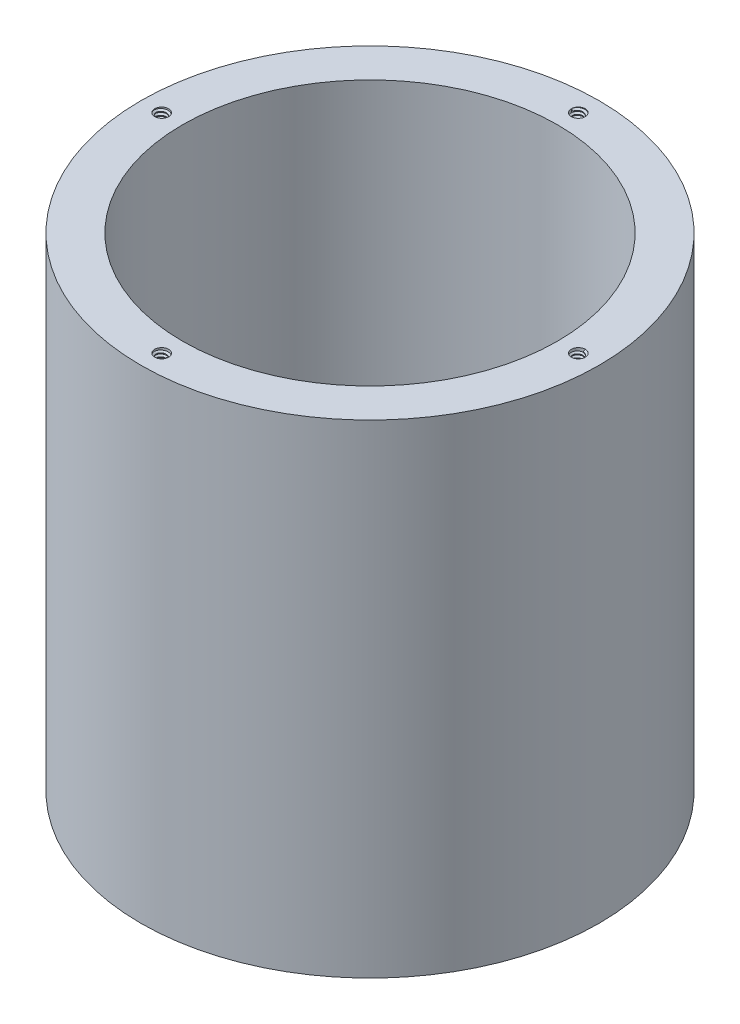
SolidWorks part; units mm, degrees
material "1060 Alloy"
ref_plane "Front Plane" through (0, 0, 0) normal (0, 0, 1) x (1, 0, 0)
ref_plane "Top Plane" through (0, 0, 0) normal (0, 1, 0) x (1, 0, 0)
ref_plane "Right Plane" through (0, 0, 0) normal (1, 0, 0) x (0, 0, -1)
sketch "Sketch1" plane through (0, 0, 0) normal (0, 1, 0) x (1, 0, 0)
  circle A0 centre (0, 0) radius 16.5
  circle A1 centre (0, 0) radius 13.5
  dimension "D1" = 33
  dimension "D2" = 27
extrude "Boss-Extrude1" add sketch "Sketch1" along normal blind 34.8
sketch "Sketch2" plane through (0, 34.8, 0) normal (0, 1, 0) x (1, 0, 0)
  circle A0 centre (0, 15) radius 0.5
  circle A2 centre (0, 0) radius 13.5 construction
  dimension "D1" = 1
  dimension "D2" = 15
extrude "Cut-Extrude1" cut sketch "Sketch2" against normal blind 2
thread "Thread1" pitch 0.25 method extrude profile "Thread Profile1" start angle 0, offset 0, length 2, pitch 0.25, diameter 1
ref_plane "Plane1" through (-0.5, 34.8, -15) normal (0, 0, 1) x (-1, 0, 0)
sketch "Thread Profile1" plane through (-0.5, 34.8, -15) normal (0, 0, 1) x (-1, 0, 0)
  line L0 (0, 0) -> (0, 0.25) construction
  line L11 (0, 0) -> (0, 0.2187)
  line L12 (0, 0.2187) -> (-0.1353, 0.1406)
  line L13 (-0.1353, 0.1406) -> (-0.1353, 0.0781)
  line L15 (-0.1353, 0.0781) -> (0, 0)
  line L17 (-0.1353, 0.1094) -> (0, 0.1094) construction
  point P2 (0, 0)
  dimension "Pitch" = 0.25
  dimension "Profile_Angle" = 60
  dimension "Profile_Land" = 0.0625
  dimension "Profile_Height" = 0.1353
pattern_circular "CirPattern1" count 4 over 360 about axis through (0, 34.8, 0) along (0, 1, 0) of "Cut-Extrude1", "Thread1"
sketch "Sketch5" plane through (0, 0, 0) normal (0, -1, 0) x (1, 0, 0)
  circle A0 centre (0, 15) radius 0.5
  dimension "D1" = 1
  dimension "D2" = 15
extrude "Cut-Extrude2" cut sketch "Sketch5" against normal blind 2
thread "Thread2" pitch 0.25 method extrude profile "Thread Profile2" start angle 0, offset 0, length 2, pitch 0.25, diameter 1
ref_plane "Plane2" through (0.5, 0, 15) normal (0, 0, 1) x (1, 0, 0)
sketch "Thread Profile2" plane through (0.5, 0, 15) normal (0, 0, 1) x (1, 0, 0)
  line L0 (0, 0) -> (0, 0.25) construction
  line L11 (0, 0) -> (0, 0.2187)
  line L12 (0, 0.2187) -> (-0.1353, 0.1406)
  line L13 (-0.1353, 0.1406) -> (-0.1353, 0.0781)
  line L15 (-0.1353, 0.0781) -> (0, 0)
  line L17 (-0.1353, 0.1094) -> (0, 0.1094) construction
  point P2 (0, 0)
  dimension "Pitch" = 0.25
  dimension "Profile_Angle" = 60
  dimension "Profile_Land" = 0.0625
  dimension "Profile_Height" = 0.1353
pattern_circular "CirPattern2" count 4 over 360 about axis through (0, 0, 0) along (0, 1, 0) of "Cut-Extrude2", "Thread2"
